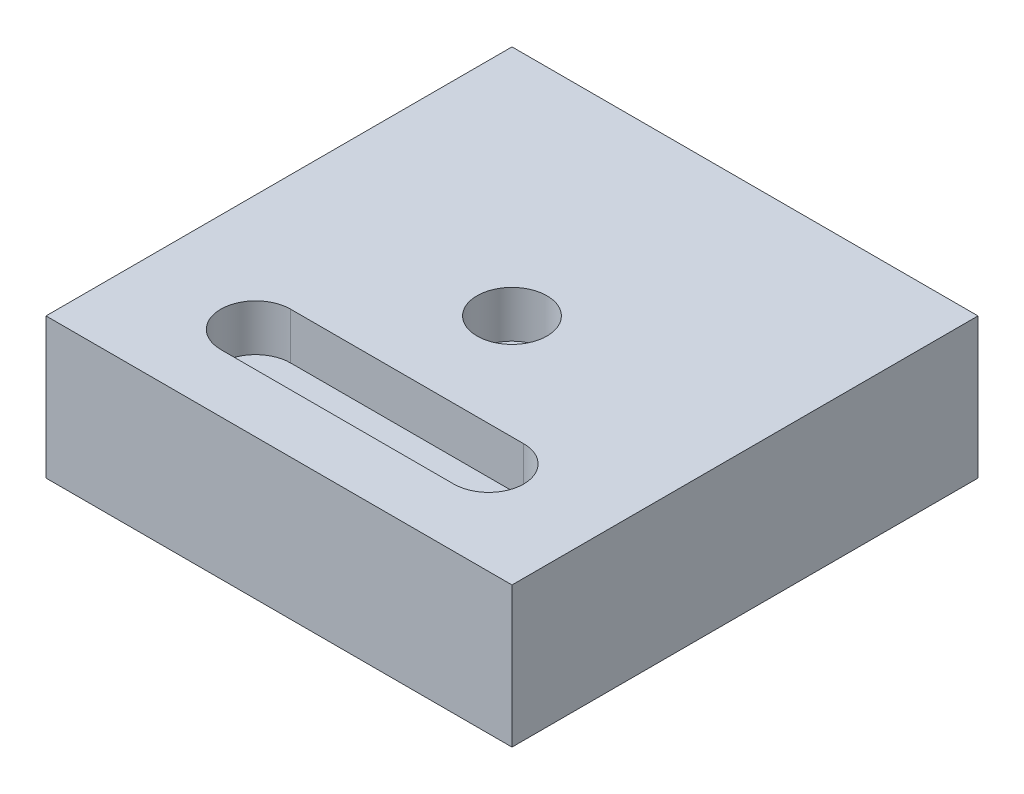
SolidWorks part; units mm, degrees
note: '?' marks a value the reader was unsure of.
ref_plane "前视基准面" through (0, 0, 0) normal (0, 0, 1) x (1, 0, 0)
ref_plane "上视基准面" through (0, 0, 0) normal (0, 1, 0) x (1, 0, 0)
ref_plane "右视基准面" through (0, 0, 0) normal (1, 0, 0) x (0, 0, -1)
other "Configuration Table"
sketch "草图2" plane through (0, 0, 0) normal (0, 1, 0) x (1, 0, 0)
  line L0 (80, 50) -> (80, -50)
  line L1 (-50, -50) -> (50, -50)
  line L2 (-50, -50) -> (-50, 50)
  line L3 (-50, 50) -> (50, 50)
  line L4 (50, -50) -> (50, 50)
  line L5 (0, 50) -> (0, -50) construction
  line L6 (-50, 0) -> (50, 0) construction
  line L7 (80, -50) -> (180, -50)
  line L8 (180, -50) -> (80, 50)
  point P0 (0, 0)
  dimension "D1" = 100
  dimension "D2" = 100
  dimension "D3" = 30
extrude "凸台-拉伸1" add sketch "草图2" along normal blind 30.1441
ref_axis "基准轴1" through (0, 0, 0) along (0, 1, 0)?
mirror "镜向2" about plane through (0, 0, 0) normal (1, 0, 0) of bodies 107
sketch "草图3" plane through (0, 30.1441, 0) normal (0, 1, 0) x (1, 0, 0)
  line L0 (-25, -30) -> (25, -30) construction
  line L1 (-25, -22.5) -> (25, -22.5)
  line L2 (-25, -37.5) -> (25, -37.5)
  line L3 (0, 0) -> (0, -30) construction
  circle A0 centre (0, 0) radius 7.5
  arc A1 (-25, -22.5) -> (-25, -37.5) centre (-25, -30) ccw
  arc A2 (25, -37.5) -> (25, -22.5) centre (25, -30) ccw
  point P5 (0, -30)
  dimension "D1" = 15
  dimension "D2" = 50
  dimension "D3" = 15
  dimension "D4" = 30
extrude "切除-拉伸1" cut sketch "草图3" against normal blind 10
sketch "草图6" plane through (0, 30.1441, 0) normal (0, 1, 0) x (1, 0, 0)
  line L0 (-80, 50) -> (-180, -50) construction
  line L1 (-180, -50) -> (-80, -50) construction
  line L2 (-80, -50) -> (-80, 50) construction
  line L3 (180, -50) -> (80, 50) construction
  line L4 (80, 50) -> (80, -50) construction
  line L5 (80, -50) -> (180, -50) construction
  line L6 (-80, 50) -> (-180, -50)
  line L7 (-180, -50) -> (-80, -50)
  line L8 (-80, -50) -> (-80, 50)
  line L9 (180, -50) -> (80, 50)
  line L10 (80, 50) -> (80, -50)
  line L11 (80, -50) -> (180, -50)
  line L12 (-80, 50) -> (-180, -50)
  line L13 (-180, -50) -> (-80, -50)
  line L14 (-80, -50) -> (-80, 50)
  line L15 (180, -50) -> (80, 50)
  line L16 (80, 50) -> (80, -50)
  line L17 (80, -50) -> (180, -50)
extrude "切除-拉伸3" cut sketch "草图6" against normal through all contours L10 L11 L9 | L6 L7 L8
